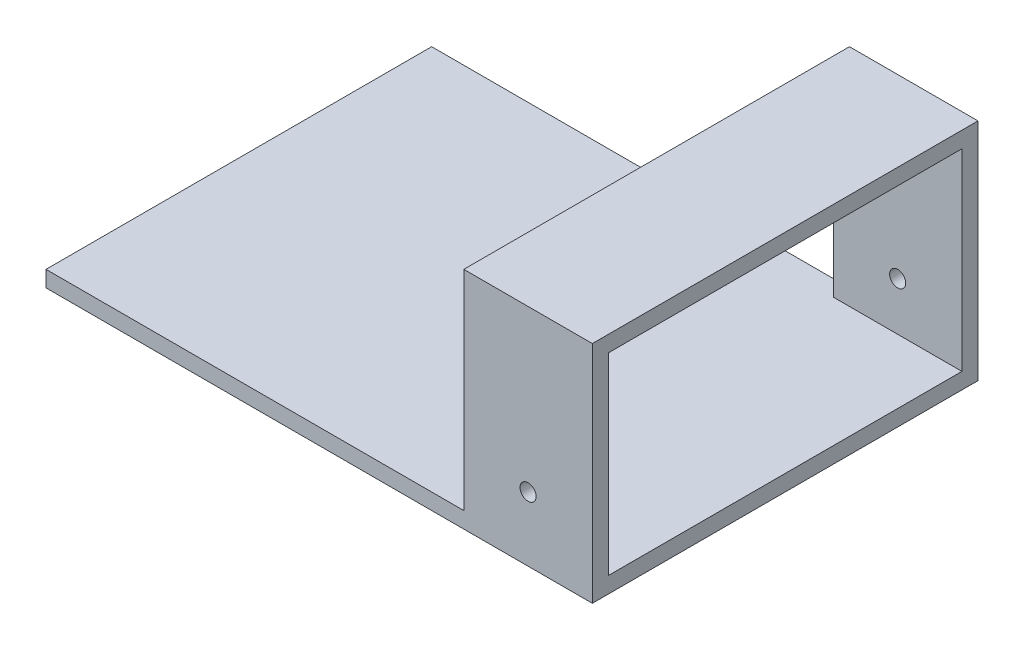
SolidWorks part; units mm, degrees
ref_plane "Front Plane" through (0, 0, 0) normal (0, 0, 1) x (1, 0, 0)
ref_plane "Top Plane" through (0, 0, 0) normal (0, 1, 0) x (1, 0, 0)
ref_plane "Right Plane" through (0, 0, 0) normal (1, 0, 0) x (0, 0, -1)
sketch "Sketch1" plane through (0, 0, 0) normal (0, 1, 0) x (1, 0, 0)
  line L0 (-215.9, 152.4) -> (-215.9, 0)
  line L1 (0, 0) -> (-50.8, 0)
  line L2 (0, 0) -> (0, 152.4)
  line L3 (0, 152.4) -> (-50.8, 152.4)
  line L4 (-50.8, 0) -> (-50.8, 152.4)
  line L5 (-50.8, 152.4) -> (-215.9, 152.4)
  line L15 (-215.9, 0) -> (0, 0)
  line L19 (-215.9, 152.4) -> (0, 152.4)
  dimension "D1" = 152.4
  dimension "D2" = 50.8
  dimension "D3" = 215.9
extrude "Boss-Extrude1" add sketch "Sketch1" along normal blind 6.35 contours L0 L15 L4 L5 region at (-133.35, 0, -76.2)
extrude "Boss-Extrude2" add sketch "Sketch1<7>" along normal blind 88.9 contours L4 L1 L2 L3 region at (-25.4, 0, -76.2)
sketch "Sketch1<7>" plane through (0, 0, 0) normal (0, 1, 0) x (1, 0, 0) same geometry as "Sketch1"
sketch "Sketch29" plane through (-50.8, 0, 0) normal (-1, 0, 0) x (0, 0, 1)
  line L0 (-152.4, 88.9) -> (-152.4, 6.35) construction
  line L1 (-146.05, 82.55) -> (-6.35, 82.55)
  line L2 (-146.05, 82.55) -> (-146.05, 6.35)
  line L3 (-146.05, 6.35) -> (-6.35, 6.35)
  line L4 (-6.35, 82.55) -> (-6.35, 6.35)
  line L5 (0, 88.9) -> (-152.4, 88.9) construction
  line L6 (-152.4, 6.35) -> (0, 6.35) construction
  line L7 (0, 88.9) -> (0, 6.35) construction
  dimension "D1" = 6.35
  dimension "D2" = 6.35
  dimension "D3" = 0
  dimension "D4" = 6.35
extrude "Cut-Extrude4" cut sketch "Sketch29" against normal through all
hole_wizard "1/4 (0.25) Diameter Hole2" positions "Sketch30" profile "Sketch31" hole size "1/4" standard "ANSI Inch" end condition through all
sketch "Sketch30" plane through (0, 0, -152.4) normal (0, 0, -1) x (-1, 0, 0)
  line L0 (0, 0) -> (215.9, 0) construction
  line L1 (0, 88.9) -> (0, 0) construction
  point P0 (25.4, 25.4)
  dimension "D1" = 25.4
  dimension "D2" = 25.4
sketch "Sketch31" plane through (-25.4, 25.4, -152.4) normal (1, 0, 0) x (0, 1, 0)
  line L0 (0, 0) -> (0, 152.4)
  line L1 (0, 152.4) -> (3.175, 152.4)
  line L2 (3.175, 152.4) -> (3.175, 0)
  line L5 (3.175, 0) -> (0, 0)
  line L11 (0, -6.35) -> (0, 107.95) construction
  dimension "Thru Hole Dia." = 6.35
  dimension "Thru Hole Depth" = 152.4
